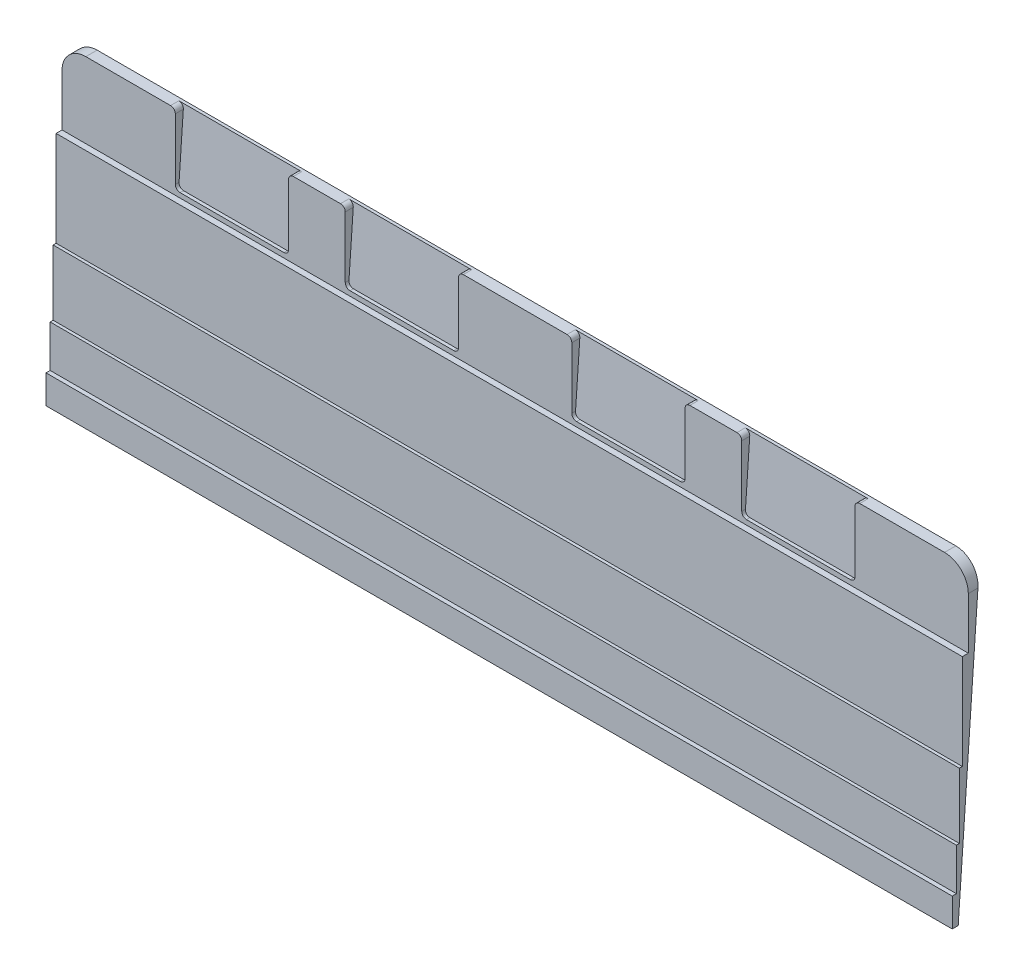
SolidWorks part; units mm, degrees
material "Glass"
ref_plane "Front Plane" through (0, 0, 0) normal (0, 0, 1) x (1, 0, 0)
ref_plane "Top Plane" through (0, 0, 0) normal (0, 1, 0) x (1, 0, 0)
ref_plane "Right Plane" through (0, 0, 0) normal (1, 0, 0) x (0, 0, -1)
ref_plane "Plane1" through (-149.225, 0, 0) normal (-1, 0, 0) x (0, 0, 1)
ref_plane "Plane2" through (155.5753, 0, 0) normal (1, 0, 0) x (0, 0, -1)
sketch "Sketch1" plane through (-149.225, 0, 0) normal (-1, 0, 0) x (0, 0, 1)
  line L0 (-3.3962, -64.0237) -> (2.6038, -64.0237) construction
  line L1 (-2, -64.0237) -> (-3.3962, -64.0237)
  line L2 (-4, 84.0184) -> (-4, -73.6248) construction
  line L3 (-4, -73.6248) -> (-11.2027, 29.3782)
  line L4 (-3.3962, -64.0237) -> (-3.3962, -49.8988)
  line L5 (14.1038, -73.6248) -> (-62.5482, -73.6248) construction
  line L6 (-4, -73.6248) -> (-15.0962, 85.0583) construction
  line L7 (-3.3962, -49.8988) -> (-4.3962, -49.8988)
  line L9 (-4.3962, -49.8988) -> (-4.3962, -27.9763)
  line L10 (-4.3962, -27.9763) -> (-5.3962, -27.9763)
  line L14 (-2, -73.6248) -> (-4, -73.6248)
  line L16 (-2, -73.6248) -> (-2, -64.0237)
  line L17 (-5.3962, -27.9763) -> (-5.3962, 4.0237)
  line L19 (-5.3962, 4.0237) -> (-7.3962, 4.0237)
  line L20 (-7.3962, 4.0237) -> (-7.3962, 29.3782)
  line L21 (-7.3962, 29.3782) -> (-11.2027, 29.3782)
  dimension "D1" = 73.6248
  dimension "D2" = 2
  dimension "D3" = 4
extrude "Boss-Extrude1" add sketch "Sketch1" against normal up to surface (304.8003 mm away) up to plane "Plane2"
fillet "Fillet1" radius 8 2 edges at (155.5753, 29.3782, -9.2994) (-149.225, 29.3782, -9.2994)
sketch "Sketch2" plane through (0, 0, -7.3962) normal (0, 0, 1) x (1, 0, 0)
  line L0 (3.1753, 121.2498) -> (3.1753, -113.2057) construction
  line L1 (10.1748, 54.6246) -> (-3.8242, 54.6246) construction
  line L2 (60.3261, 5.6237) -> (22.2253, 5.6237)
  line L3 (-104.1252, 35.5747) -> (-118.1245, 35.5747) construction
  line L12 (-111.1249, 5.6237) -> (-111.1249, 29.3782)
  line L13 (-111.1249, 29.3782) -> (-73.0249, 29.3782)
  line L14 (-73.0249, 29.3782) -> (-73.0249, 5.6237)
  line L15 (-66.0252, 35.5747) -> (-80.0245, 35.5747) construction
  line L16 (-53.9756, 5.6237) -> (-53.9756, 29.3782)
  line L17 (-53.9756, 29.3782) -> (-15.8747, 29.3782)
  line L18 (-15.8747, 29.3782) -> (-15.8747, 5.6237)
  line L19 (-46.9752, 35.5747) -> (-60.9759, 35.5747) construction
  line L20 (-8.8752, 35.5747) -> (-22.8742, 35.5747) construction
  line L21 (-111.1249, 5.6237) -> (-73.0249, 5.6237)
  line L22 (-53.9756, 5.6237) -> (-15.8747, 5.6237)
  line L23 (117.4754, 5.6237) -> (79.3754, 5.6237)
  line L24 (22.2253, 29.3782) -> (22.2253, 5.6237)
  line L25 (60.3261, 29.3782) -> (22.2253, 29.3782)
  line L26 (60.3261, 5.6237) -> (60.3261, 29.3782)
  line L27 (79.3754, 29.3782) -> (79.3754, 5.6237)
  line L28 (117.4754, 29.3782) -> (79.3754, 29.3782)
  line L29 (117.4754, 5.6237) -> (117.4754, 29.3782)
  line L31 (147.5753, 29.3782) -> (-141.225, 29.3782) construction
  line L33 (155.5753, 4.0237) -> (-149.225, 4.0237) construction
  point P12 (3.1753, 54.6246)
  point P24 (-111.1249, 35.5747)
  point P27 (-73.0249, 35.5747)
  point P30 (-53.9756, 35.5747)
  point P33 (-15.8747, 35.5747)
  dimension "D1" = 1.6
extrude "Cut-Extrude1" cut sketch "Sketch2" against normal offset from surface (2.804 mm away) 1 contours L12 L21 L14 | L16 L22 L18 | L2 L26 L24 | L23 L29 L27 region at (41.2757, 17.5009, -7.3962) region at (-92.0749, 17.5009, -7.3962) region at (-34.9251, 17.5009, -7.3962) region at (98.4254, 17.5009, -7.3962) up to face at (3.1751, -7.0705, -8.6539)
fillet "Fillet2" radius 1.6 8 edges at (-15.8747, 5.6237, -7.9677) (-53.9756, 5.6237, -7.9677) (-111.1249, 5.6237, -7.9677) (-73.0249, 5.6237, -7.9677) (79.3754, 5.6237, -7.9677) (117.4754, 5.6237, -7.9677) (60.3261, 5.6237, -7.9677) (22.2253, 5.6237, -7.9677)
fillet "Fillet3" radius 1.6 8 edges at (117.4754, 29.3782, -8.7982) (60.3261, 29.3782, -8.7982) (79.3754, 29.3782, -8.7982) (22.2253, 29.3782, -8.7982) (-15.8747, 29.3782, -8.7982) (-53.9756, 29.3782, -8.7982) (-73.0249, 29.3782, -8.7982) (-111.1249, 29.3782, -8.7982)
